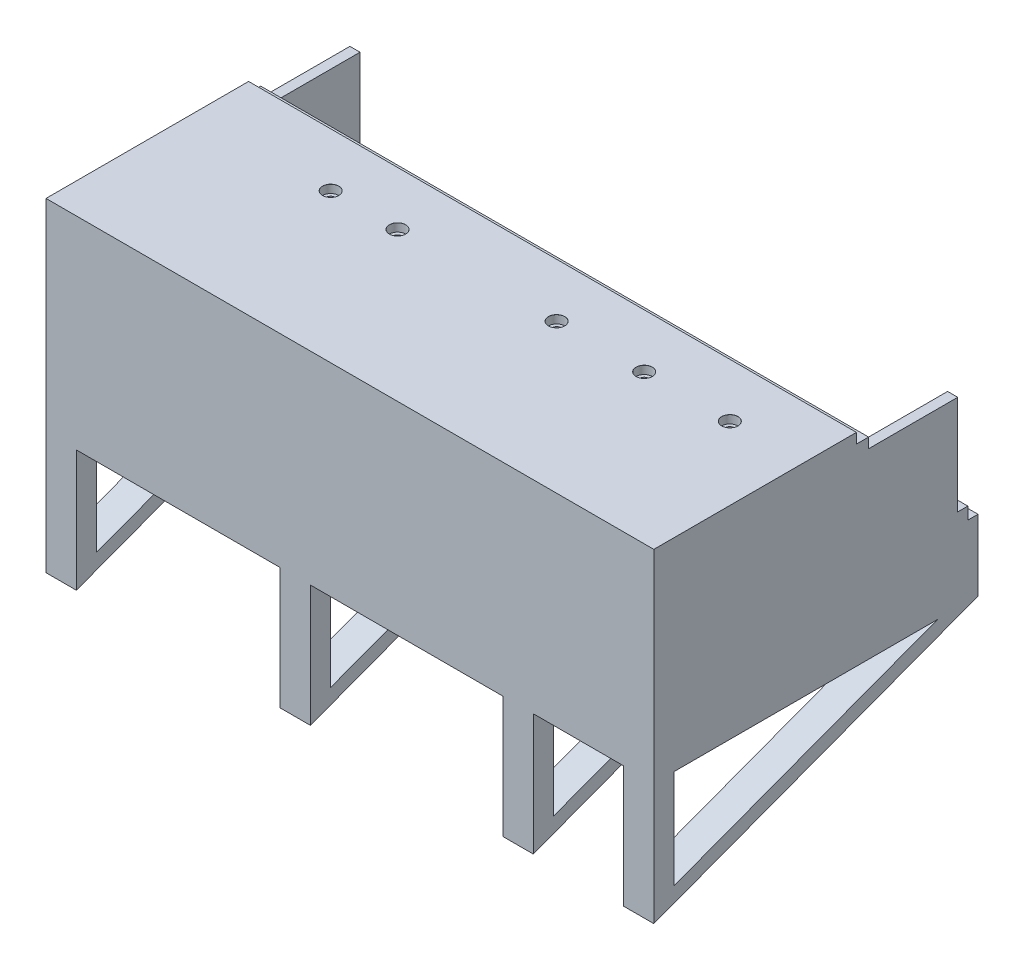
SolidWorks part; units mm, degrees
ref_plane "Front Plane" through (0, 0, 0) normal (0, 0, 1) x (1, 0, 0)
ref_plane "Top Plane" through (0, 0, 0) normal (0, 1, 0) x (1, 0, 0)
ref_plane "Right Plane" through (0, 0, 0) normal (1, 0, 0) x (0, 0, -1)
sketch "LeftSideSketch" plane through (0, 0, 0) normal (1, 0, 0) x (0, 0, -1)
  line L0 (0, 0) -> (160, 0)
  line L1 (160, 0) -> (160, -100)
  line L3 (0, -100) -> (0, 0)
  line L5 (10, -10) -> (10, -90)
  line L6 (10, -90) -> (150, -90)
  line L7 (150, -90) -> (150, -10)
  line L9 (10, -10) -> (150, -10)
  line L10 (0, -100) -> (0, -160)
  line L11 (0, -160) -> (160, -100)
  line L12 (10, -100) -> (10, -148.774)
  line L13 (10, -148.774) -> (140.064, -100)
  line L15 (0, -100) -> (10, -100)
  line L16 (10, -100) -> (140.064, -100)
  line L17 (140.064, -100) -> (160, -100)
  line L18 (100, 0) -> (100, -5)
  line L19 (100, -5) -> (106, -5)
  line L20 (106, -5) -> (106, -10)
  line L21 (160, -65) -> (155, -65)
  line L22 (155, -65) -> (155, -59)
  line L23 (155, -59) -> (150, -59)
  point P19 (157.5, -65)
  dimension "D1" = 160
  dimension "D2" = 100
  dimension "D3" = 10
  dimension "D4" = 10
  dimension "D5" = 10
  dimension "D6" = 10
  dimension "D7" = 7
  dimension "D8" = 10
  dimension "D9" = 5
  dimension "D10" = 60
  dimension "D11" = 5
  dimension "D12" = 35
  dimension "D13" = 100
  dimension "D14" = 6
  dimension "D15" = 6
extrude "walls" add sketch "LeftSideSketch" along normal blind 300 contours L3 L1 L0 L5 L9 L7 L6 region at (0, -1.8868, -50)
extrude "leg1" add sketch "LeftSideSketch<4>" along normal blind 15 contours L10 L11 L13 L12 region at (0, -101.7088, -5)
sketch "LeftSideSketch<4>" plane through (0, 0, 0) normal (1, 0, 0) x (0, 0, -1) same geometry as "LeftSideSketch"
extrude "leg4" add sketch "LeftSideSketch<5>" against normal blind 15 from surface contours L10 L11 L13 L12 region at (0, -101.7088, -5) starting at face at (300, -47, -97.2857)
sketch "LeftSideSketch<5>" plane through (0, 0, 0) normal (1, 0, 0) x (0, 0, -1) same geometry as "LeftSideSketch"
ref_plane "refPlane1" through (123, 0, 0) normal (1, 0, 0) x (0, 0, -1)
ref_plane "refPlane2" through (233, 0, 0) normal (1, 0, 0) x (0, 0, -1)
extrude "leg2" add sketch "LeftSideSketch<7>" along normal mid plane 15 from surface contours L17 L13 L12 L15 L10 L11 region at (0, -101.7088, -5) starting at plane "refPlane1"
sketch "LeftSideSketch<7>" plane through (0, 0, 0) normal (1, 0, 0) x (0, 0, -1) same geometry as "LeftSideSketch"
extrude "leg3" add sketch "LeftSideSketch<9>" along normal mid plane 15 from surface contours L17 L13 L12 L15 L10 L11 region at (0, -101.7088, -5) starting at plane "refPlane2"
sketch "LeftSideSketch<9>" plane through (0, 0, 0) normal (1, 0, 0) x (0, 0, -1) same geometry as "LeftSideSketch"
extrude "right wall" add sketch "LeftSideSketch<10>" along normal blind 5 contours L9 L5 L6 L7 region at (0, -50, -80)
sketch "LeftSideSketch<10>" plane through (0, 0, 0) normal (1, 0, 0) x (0, 0, -1) same geometry as "LeftSideSketch"
extrude "left wall" add sketch "LeftSideSketch<11>" against normal blind 5 from surface contours L9 L5 L6 L7 region at (0, -50, -80) starting at face at (300, -116.258, -53.3547)
sketch "LeftSideSketch<11>" plane through (0, 0, 0) normal (1, 0, 0) x (0, 0, -1) same geometry as "LeftSideSketch"
sketch "TableSketch" plane through (0, -90, 0) normal (0, 1, 0) x (1, 0, 0)
  line L0 (40, 117.5) -> (40, 52.5)
  line L1 (40, 52.5) -> (200, 52.5)
  line L2 (200, 52.5) -> (200, 117.5)
  line L3 (40, 117.5) -> (200, 117.5)
  line L4 (147.5, 106.25) -> (190, 106.25)
  line L6 (190, 106.25) -> (190, 63.75)
  line L7 (190, 63.75) -> (177.75, 63.75)
  line L8 (147.5, 63.75) -> (147.5, 106.25)
  line L11 (295, 10) -> (5, 10) construction
  line L12 (200, 52.5) -> (137.5, 52.5)
  line L13 (200, 52.5) -> (200, 117.5)
  line L14 (200, 117.5) -> (137.5, 117.5)
  line L15 (137.5, 52.5) -> (137.5, 117.5)
  line L16 (159.75, 63.75) -> (159.75, 52.5)
  line L17 (177.75, 63.75) -> (177.75, 52.5)
  line L18 (295, 150) -> (295, 10) construction
  line L19 (159.75, 63.75) -> (147.5, 63.75)
  circle A0 centre (78.75, 85) radius 27
  circle A1 centre (78.75, 85) radius 19.2
  circle A6 centre (78.75, 58) radius 3
  circle A7 centre (61.3947, 64.3168) radius 3
  circle A8 centre (52.1602, 80.3115) radius 3
  circle A9 centre (55.3673, 98.5) radius 3 [skipped]
  circle A10 centre (69.5155, 110.3717) radius 3 [skipped]
  circle A11 centre (87.9845, 110.3717) radius 3 [skipped]
  circle A12 centre (102.1327, 98.5) radius 3 [skipped]
  circle A13 centre (105.3398, 80.3115) radius 3
  circle A14 centre (96.1053, 64.3168) radius 3
  circle A15 centre (78.75, 85) radius 30
  circle A16 centre (78.75, 85) radius 24
  point P4 (177.75, 58.125)
  point P11 (159.75, 58.125)
  point P17 (168.75, 85)
  point P20 (147.5, 85)
  point P44 (78.75, 85)
  dimension "D7" = 38.4
  dimension "D13" = 54
  dimension "D14" = 9
  dimension "D15" = 95
  dimension "D17" = 32.5
  dimension "D18" = 6
  dimension "D21" = 12.25
  dimension "D19" = 12.1602
  dimension "D20" = 27.8115
  dimension "D1" = 160
  dimension "D2" = 65
  dimension "D3" = 18
  dimension "D4" = 42.5
  dimension "D5" = 12.25
  dimension "D6" = 11.25
  dimension "D8" = 10
  dimension "D9" = 10
  dimension "D10" = 21.25
  dimension "D11" = 21.25
  dimension "D12" = 90
  dimension "D16" = 75
extrude "motor holder" add sketch "TableSketch" against normal blind 30.5 contours L15 L1 L2 L3 L6 L7 L8 | L13 L12 L15 L14 region at (168.75, -90, -116.5983)
extrude "motor holder2" cut sketch "TableSketch<5>" against normal blind 20.5 contours L8 L7 L6 L3 region at (168.75, -90, -82.2908)
sketch "TableSketch<5>" plane through (0, -90, 0) normal (0, 1, 0) x (1, 0, 0) same geometry as "TableSketch"
extrude "bearing cut" cut sketch "TableSketch<7>" against normal blind 1.74 contours A0 A7 | A0 A8 | A0 A6 | A0 A13 | A1 | A0 region at (104.0568, -90, -80.5377) region at (78.75, -90, -59.3028) region at (62.2322, -90, -65.3148) region at (53.4432, -90, -80.5377) region at (78.75, -90, -85)
sketch "TableSketch<7>" plane through (0, -90, 0) normal (0, 1, 0) x (1, 0, 0) same geometry as "TableSketch"
extrude "carousel hole" cut sketch "TableSketch<14>" against normal blind 10 contours A1 region at (78.75, -90, -85)
sketch "TableSketch<14>" plane through (0, -90, 0) normal (0, 1, 0) x (1, 0, 0) same geometry as "TableSketch"
extrude "Boss-Extrude10" add sketch "TableSketch<8>" against normal blind 15 from surface contours A0 A14 | A0 A14 | A0 A13 | A0 A13 | A0 A6 | A0 A6 | A0 A7 | A0 A7 | A0 A8 | A0 A8 region at (106.5637, -90, -80.0957) region at (104.0568, -90, -80.5377) region at (96.9041, -90, -63.3648) region at (95.2678, -90, -65.3148) region at (78.75, -90, -59.3028) region at (78.75, -90, -56.7573) region at (62.2322, -90, -65.3148) region at (53.4432, -90, -80.5377) region at (60.5959, -90, -63.3648) region at (50.9363, -90, -80.0957) starting at face at (78.75, -100, -65.8)
sketch "TableSketch<8>" plane through (0, -90, 0) normal (0, 1, 0) x (1, 0, 0) same geometry as "TableSketch"
extrude "funnel top" add sketch "TableSketch<9>" against normal blind 2 from surface contours A16 | A15 starting at face at (96.1053, -115, -61.3168)
sketch "TableSketch<9>" plane through (0, -90, 0) normal (0, 1, 0) x (1, 0, 0) same geometry as "TableSketch"
ref_plane "Funnel Plane (!!)" through (0, 0, -85) normal (0, 0, 1) x (1, 0, 0)
sketch "Sketch5" plane through (0, -10, 0) normal (0, -1, 0) x (1, 0, 0)
  line L0 (295, -102.5) -> (295, -44.5)
  line L1 (295, -44.5) -> (52, -44.5)
  line L2 (52, -44.5) -> (52, -102.5)
  line L3 (52, -102.5) -> (295, -102.5)
  line L4 (115, -44.5) -> (115, -102.5)
  line L5 (295, -150) -> (5, -150) construction
  line L7 (295, -106) -> (295, -10) construction
  line L8 (165, -58.5) -> (165, -88.5)
  line L9 (165, -88.5) -> (192, -88.5)
  line L10 (235.25, -88.5) -> (235.25, -58.5)
  line L11 (235.25, -58.5) -> (208.25, -58.5)
  line L12 (250.5, -58.5) -> (250.5, -88.5)
  line L13 (250.5, -88.5) -> (277.5, -88.5)
  line L14 (277.5, -88.5) -> (277.5, -58.5)
  line L15 (277.5, -58.5) -> (250.5, -58.5)
  line L16 (192, -58.5) -> (192, -88.5)
  line L17 (208.25, -58.5) -> (208.25, -88.5)
  line L18 (208.25, -88.5) -> (235.25, -88.5)
  line L19 (192, -58.5) -> (165, -58.5)
  point P6 (115, -73.5)
  point P23 (165, -73.5)
  point P24 (277.5, -73.5)
  point P25 (178.5, -73.5)
  point P26 (67, -73.5)
  point P27 (221.75, -73.5)
  point P28 (264, -73.5)
  point P29 (0, 0)
  point P30 (0, 0)
  point P32 (100, -73.5)
  dimension "D1" = 58
  dimension "D2" = 243
  dimension "D3" = 63
  dimension "D4" = 47.5
  dimension "D5" = 0
  dimension "D6" = 29
  dimension "D7" = 15
  dimension "D8" = 27
  dimension "D9" = 27
  dimension "D10" = 50
  dimension "D11" = 70.25
  dimension "D12" = 27
  dimension "D13" = 15.25
  dimension "D14" = 30
  dimension "D15" = 13.5
  dimension "D16" = 15
  dimension "D17" = 15
  dimension "D18" = 13.5
  dimension "D19" = 13.5
sketch "Sketch6" plane through (0, 0, -85) normal (0, 0, 1) x (1, 0, 0)
  line L0 (78.75, -1117) -> (78.75, 48883) construction
  line L1 (48.75, -117) -> (108.75, -117) construction
  line L2 (48.75, -117) -> (54.75, -117)
  line L3 (54.75, -117) -> (54.75, -118.5)
  line L4 (54.75, -118.5) -> (77.06, -138.5)
  line L5 (77.06, -138.5) -> (75.57, -138.5)
  line L6 (75.57, -138.5) -> (48.75, -118.5)
  line L7 (48.75, -118.5) -> (48.75, -117)
  line L8 (54.75, -117) -> (102.75, -117) construction
  point P5 (78.75, -117)
  point P14 (0, 0)
  point P15 (54.8503, -117)
  point P16 (0, 0)
  dimension "D1" = 1.69
  dimension "D2" = 1.49
  dimension "D3" = 1.5
  dimension "D4" = 20
  dimension "D5" = 6
revolve "Revolve1" add sketch "Sketch6" angle 360 about L0
extrude "spec mouting" cut sketch "Sketch5" against normal blind 4 from surface contours L16 L19 L8 L9 | L17 L18 L10 L11 | L14 L15 L12 L13 | L4 L1 L2 L3 region at (83.5, -10, -73.5) region at (178.5, -10, -73.5) region at (221.75, -10, -73.5) region at (264, -10, -73.5) starting at face at (150, -10, -58)
sketch "Sketch12" plane through (0, 0, 0) normal (0, 1, 0) x (1, 0, 0)
  line L4 (0, 100) -> (0, 0)
  line L5 (0, 0) -> (300, 0)
  line L6 (300, 0) -> (300, 100)
  line L7 (300, 100) -> (0, 100)
  line L8 (0, 100) -> (0, 0)
  line L9 (0, 0) -> (300, 0)
  line L10 (300, 0) -> (300, 100)
  line L11 (300, 100) -> (0, 100)
  point P2 (264, 73.5)
  point P4 (221.75, 73.5)
  point P6 (178.5, 73.5)
  point P18 (221.75, 73.5)
  point P20 (264, 73.5)
  point P22 (221.75, 73.5)
  point P24 (178.5, 73.5)
  point P26 (221.75, 73.5)
  point P28 (264, 73.5)
  point P72 (67, 73.5)
  point P74 (100, 73.5)
  dimension "D1" = 0
hole_wizard "CBORE for M4 SHCS1" positions "Sketch12" profile "Sketch14" counterbore size "M4" standard "ANSI Metric"
sketch "Sketch14" plane through (100, 0, -73.5) normal (1, 0, 0) x (0, 0, 1)
  line L0 (0, 0) -> (0, 11.4421)
  line L1 (0, 11.4421) -> (2.4, 10)
  line L2 (2.4, 10) -> (2.4, 4)
  line L3 (2.4, 4) -> (4, 4)
  line L5 (4, 4) -> (4, 0.025)
  line L6 (4, 0.025) -> (4.025, 0)
  line L7 (4.025, 0) -> (0, 0)
  line L8 (-4, 0.025) -> (-4.025, 0) construction
  line L10 (0, 11.4421) -> (-2.4, 10) construction
  line L11 (0, -6.35) -> (0, 107.95) construction
  dimension "Hole Dia." = 4.8
  dimension "Hole Depth" = 10
  dimension "C'Bore Dia." = 8
  dimension "C'Bore Depth" = 4
  dimension "Near C'Sink Dia." = 8.05
  dimension "Near C'Sink Angle" = 90
  dimension "Drill Angle" = 118
